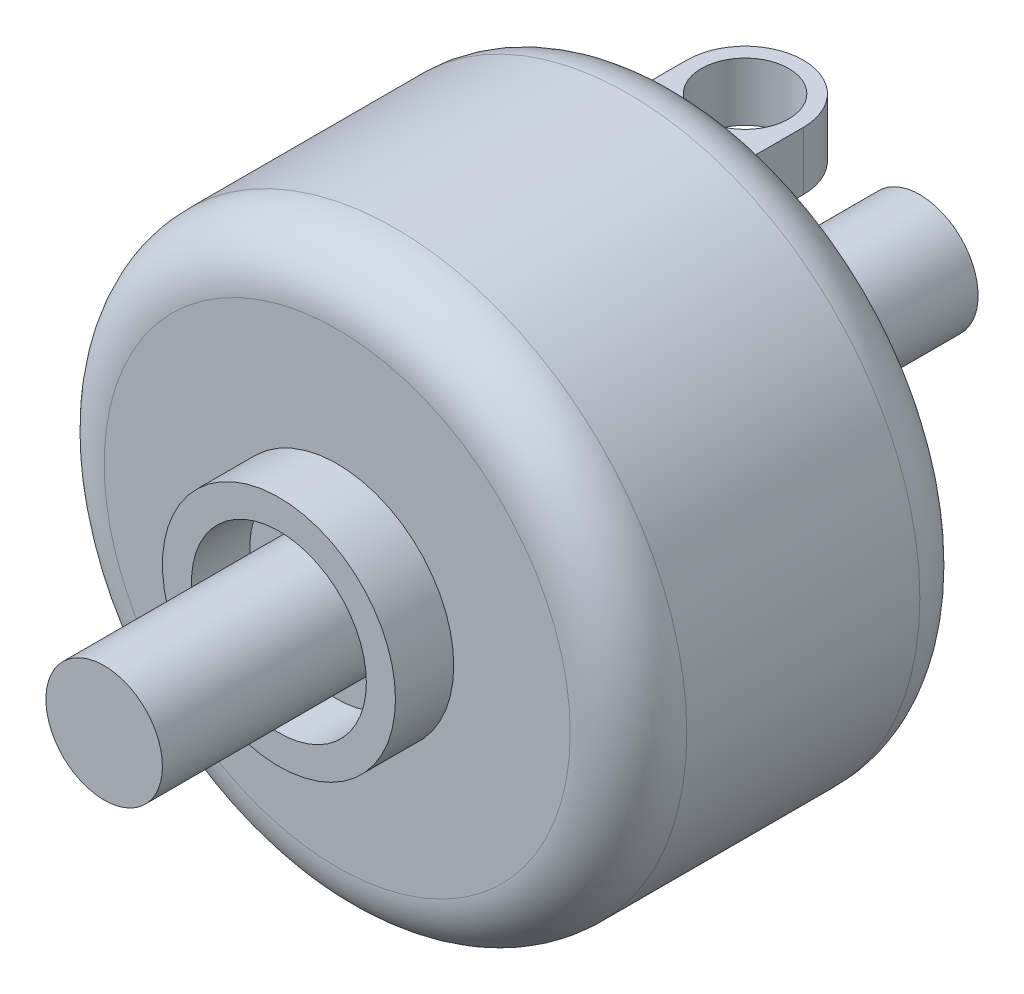
SolidWorks part; units mm, degrees
ref_plane "Front Plane" through (0, 0, 0) normal (0, 0, 1) x (1, 0, 0)
ref_plane "Top Plane" through (0, 0, 0) normal (0, 1, 0) x (1, 0, 0)
ref_plane "Right Plane" through (0, 0, 0) normal (1, 0, 0) x (0, 0, -1)
sketch "Sketch1" plane through (0, 0, 0) normal (0, 0, 1) x (1, 0, 0)
  circle A0 centre (0, 0) radius 25
  dimension "D1" = 50
extrude "Boss-Extrude1" add sketch "Sketch1" along normal blind 30
sketch "Sketch2" plane through (0, 0, 30) normal (0, 0, 1) x (1, 0, 0)
  circle A0 centre (0, 0) radius 10
  dimension "D1" = 20
extrude "Boss-Extrude2" add sketch "Sketch2" along normal blind 20
sketch "Sketch3" plane through (0, 0, 50) normal (0, 0, 1) x (1, 0, 0)
  circle A0 centre (0, 0) radius 7.5
  dimension "D1" = 15
extrude "Cut-Extrude1" cut sketch "Sketch3" against normal blind 20
sketch "Sketch4" plane through (0, 0, 30) normal (0, 0, 1) x (1, 0, 0)
  circle A0 centre (0, 0) radius 5
  dimension "D1" = 10
extrude "Boss-Extrude3" add sketch "Sketch4" along normal blind 20
sketch "Sketch5" plane through (0, 0, 0) normal (0, 0, -1) x (-1, 0, 0)
  circle A0 centre (0, 0) radius 10
  dimension "D1" = 20
extrude "Boss-Extrude4" add sketch "Sketch5" along normal blind 5
sketch "Sketch7" plane through (0, 0, 0) normal (0, 0, -1) x (-1, 0, 0)
  line L1 (5, 15) -> (-5, 15)
  line L2 (5, 15) -> (5, 20)
  line L3 (5, 20) -> (-5, 20)
  line L4 (-5, 15) -> (-5, 20)
  line L5 (5, -20) -> (-5, -20)
  line L6 (5, -20) -> (5, -15)
  line L7 (5, -15) -> (-5, -15)
  line L8 (-5, -20) -> (-5, -15)
  point P8 (0, 15)
  point P10 (0, -15)
  dimension "D1" = 5
  dimension "D2" = 10
  dimension "D3" = 10
  dimension "D4" = 5
  dimension "D5" = 15
  dimension "D6" = 15
extrude "Boss-Extrude5" add sketch "Sketch7" along normal blind 10
sketch "Sketch8" plane through (0, 20, 0) normal (0, 1, 0) x (1, 0, 0)
  line L0 (-5, 10) -> (5, 10) construction
  line L1 (5, 10) -> (5, 0) construction
  circle A0 centre (0, 5) radius 3.75
  dimension "D2" = 7.5
  dimension "D1" = 5
  dimension "D3" = 5
extrude "Cut-Extrude2" cut sketch "Sketch8" against normal up to surface (5 mm away) up to face at (0, 15, -5)
sketch "Sketch9" plane through (0, -20, 0) normal (0, -1, 0) x (-1, 0, 0)
  line L0 (5, 10) -> (5, 0) construction
  line L1 (-5, 10) -> (5, 10) construction
  circle A0 centre (0, 5) radius 3.75
  dimension "D1" = 7.5
  dimension "D2" = 5
  dimension "D3" = 5
extrude "Cut-Extrude3" cut sketch "Sketch9" against normal up to surface (5 mm away) up to face at (0, -15, -5)
fillet "Fillet1" radius 5 2 edges at (25, 0, 30) (25, 0, 0)
fillet "Fillet2" radius 5 4 edges at (5, -17.5, -10) (-5, -17.5, -10) (5, 17.5, -10) (-5, 17.5, -10)
sketch "Sketch10" plane through (0, 0, 50) normal (0, 0, 1) x (1, 0, 0)
  circle A0 centre (0, 0) radius 7.5
  circle A1 centre (0, 0) radius 10
  dimension "D1" = 15
  dimension "D2" = 20
extrude "Cut-Extrude4" cut sketch "Sketch10" against normal blind 15
sketch "Sketch11" plane through (0, 0, -5) normal (0, 0, -1) x (-1, 0, 0)
  circle A0 centre (0, 0) radius 7.5
  dimension "D1" = 15
extrude "Cut-Extrude5" cut sketch "Sketch11" against normal blind 5
sketch "Sketch12" plane through (0, 0, 0) normal (0, 0, -1) x (-1, 0, 0)
  circle A0 centre (0, 0) radius 5
  dimension "D1" = 10
extrude "Boss-Extrude6" add sketch "Sketch12" along normal blind 20
